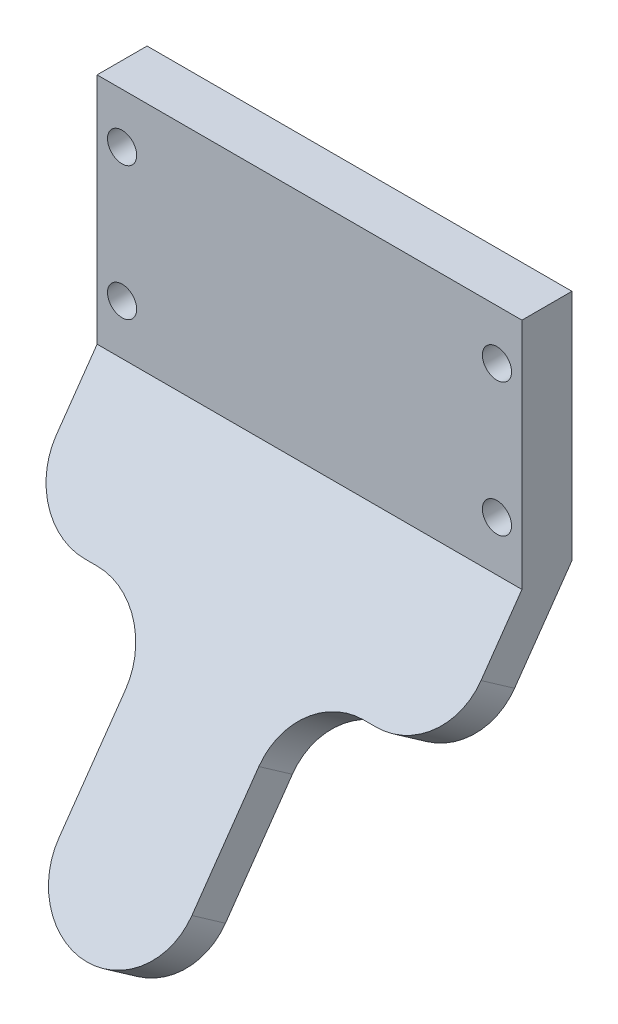
SolidWorks part; units mm, degrees
ref_plane "Plan de face" through (0, 0, 0) normal (0, 0, 1) x (1, 0, 0)
ref_plane "Plan de dessus" through (0, 0, 0) normal (0, 1, 0) x (1, 0, 0)
ref_plane "Plan de droite" through (0, 0, 0) normal (1, 0, 0) x (0, 0, -1)
sketch "Esquisse1" plane through (0, 0, 0) normal (0, 0, 1) x (1, 0, 0)
  line L1 (0, 0) -> (51, 0)
  line L2 (0, 0) -> (0, 28)
  line L3 (0, 28) -> (51, 28)
  line L4 (51, 0) -> (51, 28)
  dimension "D1" = 51
  dimension "D2" = 28
extrude "Boss.-Extru.1" add sketch "Esquisse1" along normal blind 6
sketch "Esquisse2" plane through (0, 0, 6) normal (0, 0, 1) x (1, 0, 0)
  line L0 (25.5, 0) -> (25.5, 22.4593) construction
  line L1 (0, 0) -> (51, 0) construction
  line L2 (3, 6) -> (3, 22) construction
  line L3 (0, 28) -> (0, 0) construction
  line L4 (48, 6) -> (48, 22) construction
  circle A0 centre (3, 6) radius 1.75
  circle A1 centre (3, 22) radius 1.75
  circle A2 centre (48, 22) radius 1.75
  circle A3 centre (48, 6) radius 1.75
  dimension "D4" = 3.5
  dimension "D1" = 16
  dimension "D2" = 3
  dimension "D3" = 6
extrude "Enlèv. mat.-Extru.1" cut sketch "Esquisse2" against normal through all
sketch "Esquisse3" plane through (0, 0, 0) normal (-1, 0, 0) x (0, 0, 1)
  line L0 (0, 0) -> (28.6788, -40.9576)
  line L1 (28.6788, -40.9576) -> (32.7049, -38.1385)
  line L2 (32.7049, -38.1385) -> (6, 0)
  line L3 (6, 0) -> (0, 0)
  line L4 (6, 28) -> (6, 0) construction
  dimension "D1" = 50
  dimension "D2" = 145
extrude "Boss.-Extru.2" add sketch "Esquisse3" against normal up to vertex (51 mm away) up to point (51, 28, 6)
sketch "Esquisse4" plane through (0, 0, 0) normal (0, -0.5736, -0.8192) x (-1, 0, 0)
  line L0 (-25.5, -50) -> (-25.5, 0) construction
  line L1 (-51, -50) -> (0, -50) construction
  line L2 (0, 0) -> (-51, 0) construction
  line L3 (-17.5, -50) -> (-17.5, -20)
  line L4 (-51, -50) -> (-33.5, -50)
  line L5 (-51, -50) -> (-51, -20)
  line L6 (-51, -20) -> (-33.5, -20)
  line L7 (-33.5, -50) -> (-33.5, -20)
  line L8 (0, -20) -> (-17.5, -20)
  line L9 (0, -50) -> (0, -20)
  line L10 (0, -50) -> (-17.5, -50)
  dimension "D1" = 16
  dimension "D2" = 20
extrude "Enlèv. mat.-Extru.2" cut sketch "Esquisse4" against normal up to vertex (4.9149 mm away) up to point (0, -38.1385, 32.7049)
fillet "Congé1" radius 8 6 edges at (33.5, -14.9735, 13.4846) (17.5, -14.9735, 13.4846) (33.5, -39.5481, 30.6919) (17.5, -39.5481, 30.6919) (0, -14.9735, 13.4846) (51, -14.9735, 13.4846)
